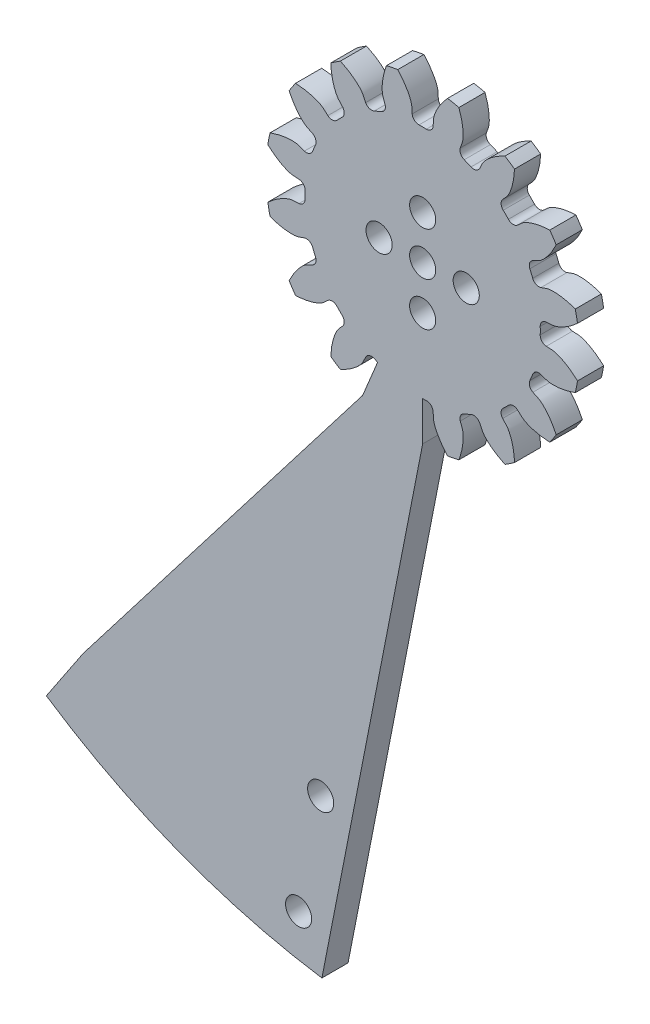
SolidWorks part; units mm, degrees
ref_plane "Front" through (0, 0, 0) normal (0, 0, 1) x (1, 0, 0)
ref_plane "Top" through (0, 0, 0) normal (0, 1, 0) x (1, 0, 0)
ref_plane "Right" through (0, 0, 0) normal (1, 0, 0) x (0, 0, -1)
ref_axis "Axis1" through (0, 0, -80.9) along (0, 0, 1)
sketch "草图1" plane through (0, 0, 0) normal (0, 0, 1) x (1, 0, 0)
  circle A0 centre (0, 0) radius 18
extrude "LaShenA" add sketch "草图1" along normal blind 3
sketch "SketchA" plane through (0, 0, 3) normal (0, 0, 1) x (1, 0, 0)
  line L0 (0, 0) -> (0, 18) construction
  arc A0 (0.4232, 13.4934) -> (-0.4232, 13.4934) centre (0, 0) ccw
  arc A1 (3.858, 18.7275) -> (-3.858, 18.7275) centre (0, 0) ccw
  arc A2 (-0.4232, 13.4934) -> (-1.2044, 14.1898) centre (-0.447, 14.253) cw
  arc A3 (1.2044, 14.1898) -> (0.4232, 13.4934) centre (0.447, 14.253) cw
  circle A4 centre (0, 0) radius 15.0351 construction
  circle A5 centre (0, 0) radius 18 construction
  circle A6 centre (0, 0) radius 13.5 construction
  circle A7 centre (0, 0) radius 16 construction
  spline S0 degree 3 poles (1.2044, 14.1898) (1.2266, 14.4552) (1.2138, 14.7739) (1.2737, 15.1106) (1.2991, 15.2114) (1.3214, 15.2911) (1.3499, 15.3823) (1.3851, 15.4846) (1.4278, 15.5978) (1.4786, 15.7214) (1.5382, 15.8552) (1.6071, 15.9987) (1.686, 16.1514) (1.7754, 16.3129) (1.876, 16.4827) (1.9884, 16.6603) (2.1129, 16.8451) (2.2502, 17.0365) (2.4007, 17.234) (2.5649, 17.4369) (2.7432, 17.6446) (2.9361, 17.8564) (3.1439, 18.0718) (3.4474, 18.3685) (3.6895, 18.585) (3.858, 18.7275) knots 0.122308 0.122308 0.122308 0.122308 0.250611 0.276296 0.287604 0.300968 0.316388 0.333864 0.353395 0.374983 0.398627 0.424327 0.452082 0.481894 0.513762 0.547685 0.583665 0.6217 0.661792 0.703939 0.748143 0.794402 0.842718 0.893089 1 1 1 1
  spline S1 degree 3 poles (-1.2044, 14.1898) (-1.2266, 14.4552) (-1.2138, 14.7739) (-1.2737, 15.1106) (-1.2991, 15.2114) (-1.3214, 15.2911) (-1.3499, 15.3823) (-1.3851, 15.4846) (-1.4278, 15.5978) (-1.4786, 15.7214) (-1.5382, 15.8552) (-1.6071, 15.9987) (-1.686, 16.1514) (-1.7754, 16.3129) (-1.876, 16.4827) (-1.9884, 16.6603) (-2.1129, 16.8451) (-2.2502, 17.0365) (-2.4007, 17.234) (-2.5649, 17.4369) (-2.7432, 17.6446) (-2.9361, 17.8564) (-3.1439, 18.0718) (-3.4474, 18.3685) (-3.6895, 18.585) (-3.858, 18.7275) knots 0.122308 0.122308 0.122308 0.122308 0.250611 0.276296 0.287604 0.300968 0.316388 0.333864 0.353395 0.374983 0.398627 0.424327 0.452082 0.481894 0.513762 0.547685 0.583665 0.6217 0.661792 0.703939 0.748143 0.794402 0.842718 0.893089 1 1 1 1
  dimension "D1" = 0.76
  dimension "Db" = 30.0702
  dimension "Da" = 36
  dimension "Df" = 27
  dimension "Dn" = 32
extrude "Cut-ExtrudeA" cut sketch "SketchA" against normal blind 3
pattern_circular "www.KYTool.cn" count 16 over 360 about axis through (0, 0, -80.9) along (0, 0, 1) of "Cut-ExtrudeA"
sketch "草图3" plane through (0, 0, 0) normal (0, 0, -1) x (-1, 0, 0)
  circle A0 centre (0, 0) radius 1.5
extrude "切除-拉伸2" cut sketch "草图3" against normal blind 10
sketch "草图4" plane through (0, 0, 0) normal (0, 0, -1) x (-1, 0, 0)
  line L0 (0, 0) -> (5, 0)
  circle A0 centre (5, 0) radius 1.5
  circle A1 centre (0, -5) radius 1.5
  circle A2 centre (-5, 0) radius 1.5
  circle A3 centre (0, 5) radius 1.5
  point P13 (0, 0)
  dimension "D1" = 4
extrude "切除-拉伸3" cut sketch "草图4" against normal blind 10 contours A3 | A0 | A1 | A2 region at (-5, -1.4576, 0) region at (0, -5, 0) region at (5, 0, 0) region at (0, 5, 0)
sketch "草图5" plane through (0, 0, 3) normal (0, 0, 1) x (1, 0, 0)
  line L0 (0, 0) -> (-5.1662, -12.4724)
  line L1 (-5.1662, -12.4724) -> (-6.8883, -16.6298)
  line L2 (0, 0) -> (0, -13.5)
  line L3 (0, -13.5) -> (0, -18)
  line L4 (-6.8883, -16.6298) -> (0, -18)
  line L5 (0, 0) -> (-3.4442, -17.3149)
  line L6 (0, 0) -> (-1.7221, -8.6575)
  line L7 (-1.7221, -8.6575) -> (-9.5221, -47.8708)
  line L8 (-3.4442, -17.3149) -> (0, -18)
  line L9 (-3.4442, -17.3149) -> (-9.0102, -45.2973)
  line L10 (0, -18) -> (-5.566, -45.9824)
  line L11 (-9.0102, -45.2973) -> (-5.566, -45.9824)
  line L12 (0, -18) -> (-11.5627, -76.8753)
  line L13 (-6.8883, -16.6298) -> (-12.4543, -44.6122)
  line L14 (-6.8883, -16.6298) -> (-18.7364, -75.4484)
  line L15 (-10.5445, -14.5881) -> (-9.4425, -15.3245)
  line L16 (0, 0) -> (-9.9935, -14.9563)
  line L18 (-43.19, -64.6385) -> (-38.9455, -58.286)
  circle A0 centre (0, 0) radius 18
  arc A1 (-5.5547, -12.3043) -> (-4.7727, -12.6282) centre (0, 0) ccw construction
  arc A2 (-0.4232, -13.4934) -> (0.4232, -13.4934) centre (0, 0) ccw construction
  circle A3 centre (0, 0) radius 77.74
  circle A4 centre (0, 0) radius 70.1
  circle A5 centre (0, 0) radius 9.0989
extrude "凸台-拉伸1" add sketch "草图5" against normal blind 3 contours A5 L7 L4 L3 L2 | A5 L0 L1 L4 L7 | L7 A0 L4 | L4 A0 L7 | L14 A4 L12 L10 L11 L9 A0 | A0 L9 L11 L10 | A4 L14 A3 L12 | A4 L18 A3 L14 region at (-4.0434, -13.2766, 3) region at (-1.3451, -13.8133, 3) region at (-10.0924, -47.4643, 3) region at (-4.7644, -17.1935, 3) region at (-2.1779, -17.708, 3) region at (-4.5241, -31.7624, 3) region at (-14.4158, -72.4733, 3) region at (-29.8465, -67.3114, 3)
sketch "草图6" plane through (0, 0, 0) normal (0, 0, -1) x (-1, 0, 0)
  line L0 (0, -13.5) -> (5.1662, -12.4724)
  line L1 (0, 0) -> (2.5831, -12.9862)
  circle A1 centre (14.2416, -71.5973) radius 1.5
  circle A3 centre (11.7054, -58.8471) radius 1.5
extrude "切除-拉伸4" cut sketch "草图6" against normal blind 3 contours A3 | A1
sketch "草图7" plane through (0, 0, 0) normal (0, 0, -1) x (-1, 0, 0)
  line L0 (6.8883, -16.6298) -> (38.9455, -58.286)
  line L1 (38.9455, -58.286) -> (31.6348, -68.8114)
  line L2 (31.6348, -68.8114) -> (17.2261, -67.9505)
  line L3 (17.2261, -67.9505) -> (6.8883, -16.6298)
extrude "凸台-拉伸2" add sketch "草图7" against normal blind 3
